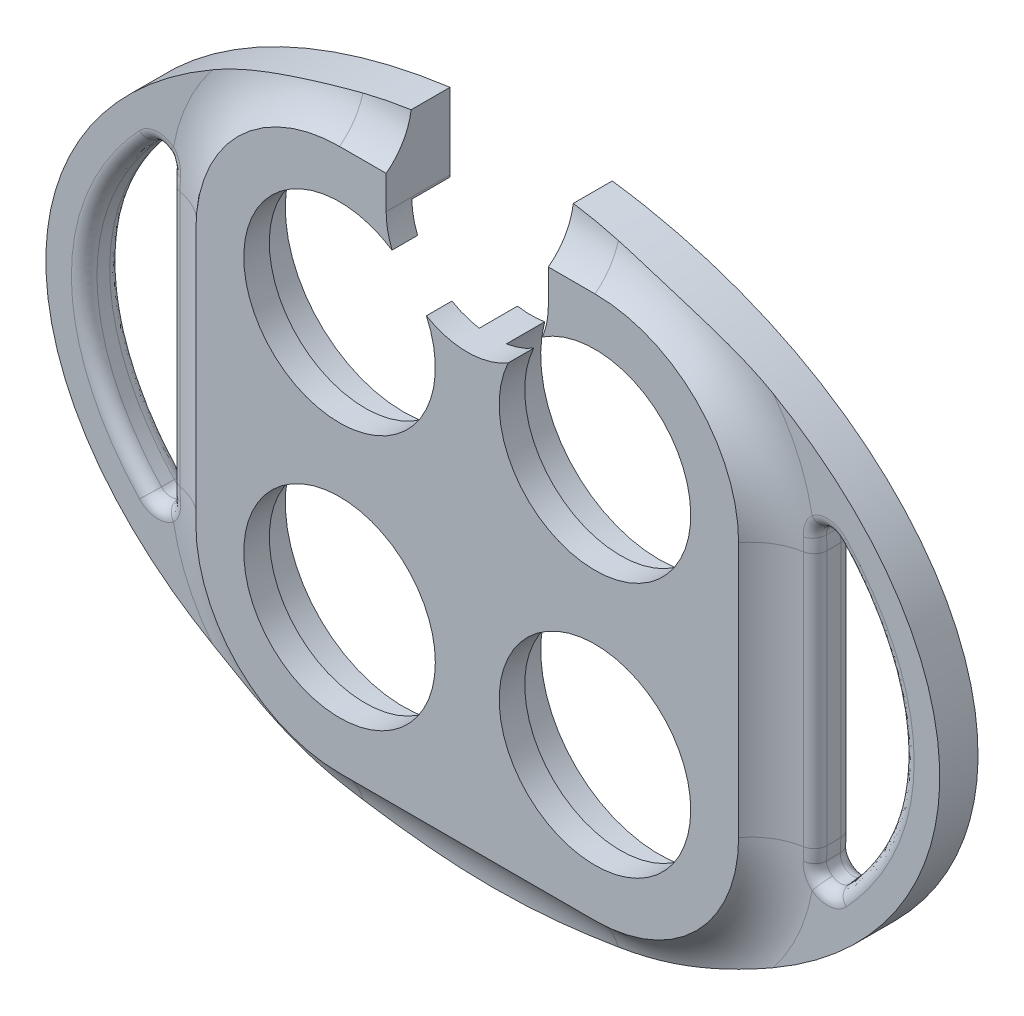
SolidWorks part; units mm, degrees
ref_plane "Front Plane" through (0, 0, 0) normal (0, 0, 1) x (1, 0, 0)
ref_plane "Top Plane" through (0, 0, 0) normal (0, 1, 0) x (1, 0, 0)
ref_plane "Right Plane" through (0, 0, 0) normal (1, 0, 0) x (0, 0, -1)
sketch "Sketch1" plane through (0, 0, 0) normal (0, 0, 1) x (1, 0, 0)
  line L0 (-10, 10) -> (10, 10) construction
  line L1 (-10, -10) -> (-10, 10) construction
  circle A0 centre (-10, 10) radius 9.25
  circle A1 centre (10, 10) radius 9.25
  circle A2 centre (-10, -10) radius 9.25
  circle A3 centre (10, -10) radius 9.25
  ellipse E0 centre (0, 0) end of major axis (35, 0) minor radius 25
  point P8 (0, 10)
  point P9 (-10, 0)
  dimension "D1" = 18.5
  dimension "D2" = 20
  dimension "D3" = 20
  dimension "D4" = 25
  dimension "D5" = 35
extrude "Plate extrude" add sketch "Sketch1" along normal mid plane 3
sketch "Sketch2" plane through (0, 0, 1.5) normal (0, 0, 1) x (1, 0, 0)
  line L0 (-10, 19.25) -> (10, 19.25) construction
  line L1 (19.25, 10) -> (19.25, -10) construction
  line L2 (10, -19.25) -> (-10, -19.25) construction
  line L3 (-19.25, -10) -> (-19.25, 10) construction
  line L4 (-10, 21.25) -> (10, 21.25)
  line L5 (21.25, 10) -> (21.25, -10)
  line L6 (10, -21.25) -> (-10, -21.25)
  line L7 (-21.25, -10) -> (-21.25, 10)
  circle A0 centre (10, -10) radius 9.25 construction
  circle A1 centre (-10, -10) radius 9.25 construction
  circle A2 centre (-10, 10) radius 9.25 construction
  circle A3 centre (10, 10) radius 9.25 construction
  arc A4 (10, -19.25) -> (19.25, -10) centre (10, -10) ccw construction
  arc A5 (-19.25, -10) -> (-10, -19.25) centre (-10, -10) ccw construction
  arc A6 (-10, 19.25) -> (-19.25, 10) centre (-10, 10) ccw construction
  arc A7 (19.25, 10) -> (10, 19.25) centre (10, 10) ccw construction
  arc A8 (21.25, 10) -> (10, 21.25) centre (10, 10) ccw
  arc A9 (10, -21.25) -> (21.25, -10) centre (10, -10) ccw
  arc A10 (-21.25, -10) -> (-10, -21.25) centre (-10, -10) ccw
  arc A11 (-10, 21.25) -> (-21.25, 10) centre (-10, 10) ccw
  circle A36 centre (-10, 10) radius 7.5
  circle A37 centre (10, 10) radius 7.5
  circle A38 centre (10, -10) radius 7.5
  circle A39 centre (-10, -10) radius 7.5
  dimension "D2" = 15
  dimension "D1" = 2
extrude "Battery end caps" add sketch "Sketch2" along normal blind 2
fillet "Cap edge rounding" radius 5 6 edges at (17.955, 17.955, 1.5) (21.25, 0, 1.5) (17.955, -17.955, 1.5) (-17.955, -17.955, 1.5) (-21.25, 0, 1.5) (-17.955, 17.955, 1.5)
sketch "Sketch3" plane through (0, 0, 1.5) normal (0, 0, 1) x (1, 0, 0)
  line L0 (-25.25, -10) -> (-25.25, 10) construction
  line L1 (-25.25, -10) -> (-25.25, 10)
  line L2 (0, -2.75) -> (0, 2.75) construction
  line L3 (25.25, -10) -> (25.25, 10)
  arc A0 (-25.25, -10) -> (-21.9523, -19.4713) centre (-10, -10) ccw construction
  arc A1 (-21.9523, 19.4713) -> (-25.25, 10) centre (-10, 10) ccw construction
  arc A2 (-25.25, -10) -> (-25.2135, -11.0543) centre (-10, -10) ccw
  arc A3 (-25.2135, 11.0543) -> (-25.25, 10) centre (-10, 10) ccw
  arc A4 (-26.9429, -11.805) -> (-25.2135, -11.0543) centre (-26.2111, -11.1234) ccw
  arc A5 (-26.9429, 11.805) -> (-25.2135, 11.0543) centre (-26.2111, 11.1234) cw
  arc A6 (26.9429, 11.805) -> (25.2135, 11.0543) centre (26.2111, 11.1234) ccw
  arc A7 (26.9429, -11.805) -> (25.2135, -11.0543) centre (26.2111, -11.1234) cw
  arc A8 (25.2135, 11.0543) -> (25.25, 10) centre (10, 10) cw
  arc A9 (25.25, -10) -> (25.2135, -11.0543) centre (10, -10) cw
  spline S0 degree 3 poles (-1722.1385, -3560.3233) (512.6888, -55.9707) (36.6594, 69.3141) (-26.8792, 11.9844) (-28.1011, 10.581) (-30.0545, 7.6658) (-30.7866, 6.1549) (-31.7587, 3.0959) (-32, 1.5476) (-32, -1.5476) (-31.7587, -3.0959) (-30.7866, -6.1549) (-30.0545, -7.6658) (-28.1011, -10.581) (-26.8792, -11.9844) (36.6592, -69.3139) (512.6844, 55.9695) (-1722.1076, 3560.2749) knots -5.23893 -5.23893 -5.23893 -5.23893 0.125 0.125 0.25 0.25 0.375 0.375 0.5 0.5 0.625 0.625 0.75 0.75 0.875 0.875 6.238906 6.238906 6.238906 6.238906 only from (-20.4565, 16.8708) to (-20.4565, -16.8708)
  spline S1 degree 3 poles (-26.9429, 11.805) (-27.7486, 10.9399) (-28.4619, 10.0424) (-30.0545, 7.6658) (-30.7866, 6.1549) (-31.7587, 3.0959) (-32, 1.5476) (-32, -1.5476) (-31.7587, -3.0959) (-30.7866, -6.1549) (-30.0545, -7.6658) (-28.4619, -10.0424) (-27.7486, -10.9399) (-26.9429, -11.805) knots 0.171183 0.171183 0.171183 0.171183 0.25 0.25 0.375 0.375 0.5 0.5 0.625 0.625 0.75 0.75 0.828817 0.828817 0.828817 0.828817
  spline S2 degree 3 poles (26.9429, 11.805) (27.7486, 10.9399) (28.4619, 10.0424) (30.0545, 7.6658) (30.7866, 6.1549) (31.7587, 3.0959) (32, 1.5476) (32, -1.5476) (31.7587, -3.0959) (30.7866, -6.1549) (30.0545, -7.6658) (28.4619, -10.0424) (27.7486, -10.9399) (26.9429, -11.805) knots 0.171183 0.171183 0.171183 0.171183 0.25 0.25 0.375 0.375 0.5 0.5 0.625 0.625 0.75 0.75 0.828817 0.828817 0.828817 0.828817
  dimension "D2" = 1
  dimension "D1" = 3
extrude "Weight reduction/wire passthru" cut sketch "Sketch3" against normal through all both and the other way through all
fillet "General rounding 1mm" radius 1 24 edges at (25.2409, 10.5274, 1.5) (25.8129, 12.0407, 1.5) (25.8129, -12.0407, 1.5) (25.2409, -10.5274, 1.5) (25.2409, 10.5274, -1.5) (25.2409, -10.5274, -1.5) (-25.2409, -10.5274, 1.5) (-25.8129, -12.0407, 1.5) (-25.8129, 12.0407, 1.5) (-25.2409, 10.5274, 1.5) (-25.2409, -10.5274, -1.5) (-25.2409, 10.5274, -1.5) (25.25, 0, 1.5) (25.25, 0, -1.5) (-25.25, 0, 1.5) (-25.25, 0, -1.5)
sketch "Sketch4" plane through (0, 0, -1.5) normal (0, 0, -1) x (-1, 0, 0)
  line L2 (-6.35, 18.65) -> (-6.35, 24.5851)
  line L3 (6.35, 18.65) -> (6.35, 24.5851)
  arc A1 (-6.35, 18.65) -> (6.35, 18.65) centre (0, 18.65) ccw
  ellipse E0 centre (0, 0) end of major axis (-35, 0) minor radius 25 construction
  ellipse E1 centre (0, 0) end of major axis (-35, 0) minor radius 25 (6.35, 24.5851) -> (-6.35, 24.5851) ccw
  dimension "D1" = 12.7
extrude ".5 inch spar hole" cut sketch "Sketch4" against normal through all both and the other way through all
